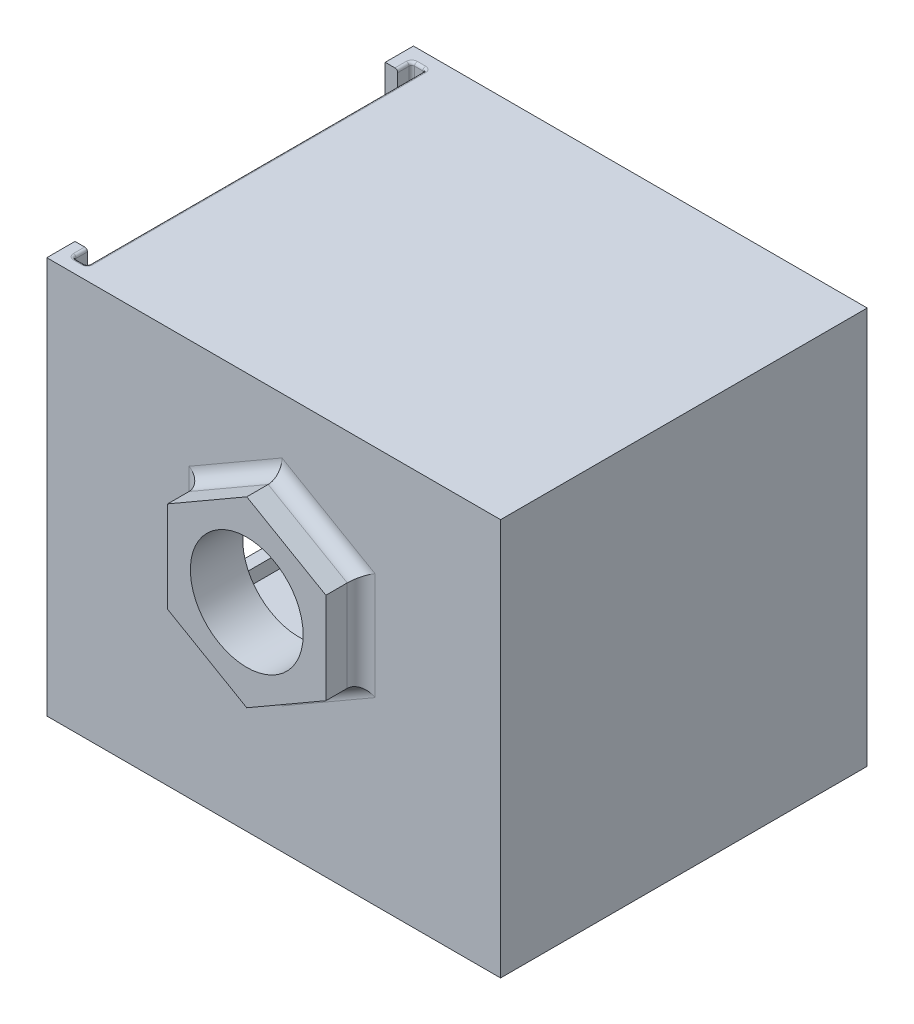
SolidWorks part; units mm, degrees
material "ABS"
ref_plane "Front Plane" through (0, 0, 0) normal (0, 0, 1) x (1, 0, 0)
ref_plane "Top Plane" through (0, 0, 0) normal (0, 1, 0) x (1, 0, 0)
ref_plane "Right Plane" through (0, 0, 0) normal (1, 0, 0) x (0, 0, -1)
sketch "Sketch1" plane through (0, 0, 0) normal (0, 1, 0) x (1, 0, 0)
  line L0 (-3.81, -5.08) -> (-3.81, 60.96)
  line L1 (0, 0) -> (71.12, 0)
  line L2 (0, 0) -> (0, 55.88)
  line L3 (0, 55.88) -> (71.12, 55.88)
  line L4 (71.12, 0) -> (71.12, 55.88)
  line L5 (-3.81, 60.96) -> (74.93, 60.96)
  line L6 (74.93, -5.08) -> (74.93, 60.96)
  line L7 (-3.81, -5.08) -> (74.93, -5.08)
  dimension "D1" = 55.88
  dimension "D2" = 71.12
  dimension "D4" = 5.08
  dimension "D5" = 5.08
  dimension "D6" = 3.81
  dimension "D3" = 3.81
extrude "Boss-Extrude1" add sketch "Sketch1" along normal blind 63.5
sketch "Sketch2" plane through (0, 0, 0) normal (0, 1, 0) x (1, 0, 0)
  line L0 (-3.81, 60.96) -> (-3.81, -5.08) construction
  line L1 (-3.81, 60.96) -> (-3.81, -5.08)
  line L2 (74.93, 60.96) -> (-3.81, 60.96) construction
  line L3 (-3.81, -5.08) -> (74.93, -5.08) construction
  line L4 (74.93, -5.08) -> (74.93, 60.96) construction
  line L5 (74.93, 60.96) -> (-3.81, 60.96)
  line L6 (-3.81, -5.08) -> (74.93, -5.08)
  line L7 (74.93, -5.08) -> (74.93, 60.96)
extrude "Boss-Extrude2" add sketch "Sketch2" against normal blind 4
sketch "Sketch3" plane through (-3.81, 0, 0) normal (-1, 0, 0) x (0, 0, 1)
  line L0 (-60.96, 63.5) -> (-60.96, -4) construction
  line L1 (-60.96, -4) -> (5.08, -4) construction
  line L3 (-47.46, 4.89) -> (-47.46, 18.86)
  line L5 (-47.46, 4.89) -> (-33.998, 4.89)
  line L6 (-33.998, 4.89) -> (-33.998, 18.86)
  line L7 (-33.998, 18.86) -> (-47.46, 18.86)
  dimension "D1" = 13.5
  dimension "D2" = 13.462
  dimension "D3" = 8.89
  dimension "D4" = 13.97
extrude "Cut-Extrude1" cut sketch "Sketch3" against normal up to next
sketch "Sketch4" plane through (-3.81, 0, 0) normal (-1, 0, 0) x (0, 0, 1)
  line L0 (5.08, -4) -> (-2.54, -4)
  line L1 (-60.96, -4) -> (5.08, -4) construction
  line L2 (-2.54, -4) -> (-2.54, 4.89)
  line L3 (-2.54, 4.89) -> (-13.462, 4.89)
  line L4 (-13.462, 4.89) -> (-13.462, 18.86)
  line L6 (-13.462, 18.86) -> (-2.54, 18.86)
  line L7 (-2.54, 18.86) -> (-2.54, 4.89)
  line M8 (5.08, 63.5) -> (-60.96, 63.5)
  dimension "D1" = 7.62
  dimension "D2" = 8.89
  dimension "D3" = 10.922
  dimension "D4" = 13.97
extrude "Cut-Extrude2" cut sketch "Sketch4" against normal up to next contours L7 L4 L3 M8 region at (-3.81, 11.875, -8.001)
sketch "Sketch5" plane through (0, -4, 0) normal (0, -1, 0) x (-1, 0, 0)
  circle A1 centre (-65.9574, 8.0585) radius 1.3693
  circle A2 centre (-13.7574, 2.8585) radius 1.6 construction
  circle A3 centre (-65.9574, 36.0085) radius 1.6 construction
  circle A4 centre (-15.1574, 51.1585) radius 1.3692
  circle A5 centre (-65.9574, 36.0085) radius 1.3693
  circle A6 centre (-13.7574, 2.8585) radius 1.3692
  circle A7 centre (-65.9574, 8.0585) radius 1.6 construction
  circle A8 centre (-15.1574, 51.1585) radius 1.6 construction
extrude "Boss-Extrude3" [suppressed] add sketch "Sketch5" against normal blind 17
fillet "Fillet1" [suppressed] radius 3
sketch "Sketch11" plane through (0, 0, 5.08) normal (0, 0, 1) x (1, 0, 0)
  line L2 (76.0425, 38.1) -> (-4.9225, 38.1) construction
  line L4 (35.56, 63.5) -> (35.56, -4) construction
  line L5 (-3.81, 63.5) -> (74.93, 63.5) construction
  line L6 (-3.81, -4) -> (74.93, -4) construction
  line L7 (49.81, 46.3272) -> (49.81, 29.8728)
  line L8 (49.81, 29.8728) -> (35.56, 21.6455)
  line L9 (49.81, 46.3272) -> (35.56, 54.5545)
  line L10 (21.31, 29.8728) -> (35.56, 21.6455)
  line L11 (21.31, 46.3272) -> (21.31, 29.8728)
  line L12 (21.31, 46.3272) -> (35.56, 54.5545)
  circle A0 centre (35.56, 38.1) radius 14.25 construction
  point P15 (35.56, 38.1)
  point P17 (49.81, 38.1)
  dimension "D1" = 28.5
  dimension "D2" = 25.4
sketch "Sketch16" plane through (-3.81, 0, 0) normal (-1, 0, 0) x (0, 0, 1)
  line L1 (-60.96, 63.5) -> (5.08, 63.5)
  line L2 (-60.96, 63.5) -> (-60.96, -4)
  line L3 (-60.96, -4) -> (5.08, -4)
  line L4 (5.08, 63.5) -> (5.08, -4)
  line L5 (-47.46, 18.86) -> (-33.998, 18.86)
  line L6 (-47.46, 18.86) -> (-47.46, 4.89)
  line L7 (-47.46, 4.89) -> (-33.998, 4.89)
  line L8 (-33.998, 18.86) -> (-33.998, 4.89)
  line L9 (-13.462, 18.86) -> (-2.54, 18.86)
  line L10 (-13.462, 18.86) -> (-13.462, 4.89)
  line L11 (-13.462, 4.89) -> (-2.54, 4.89)
  line L12 (-2.54, 18.86) -> (-2.54, 4.89)
extrude "Boss-Extrude8" add sketch "Sketch16" along normal blind 3
sketch "Sketch17" plane through (0, 63.5, 0) normal (0, 1, 0) x (1, 0, 0)
  line L1 (-6.81, 60.96) -> (74.93, 60.96)
  line L2 (-6.81, 60.96) -> (-6.81, -5.08)
  line L3 (-6.81, -5.08) -> (74.93, -5.08)
  line L4 (74.93, 60.96) -> (74.93, -5.08)
extrude "Boss-Extrude9" add sketch "Sketch17" along normal blind 4
sketch "Sketch18" plane through (0, 67.5, 0) normal (0, 1, 0) x (1, 0, 0)
  line L0 (-6.81, -5.08) -> (74.93, -5.08) construction
  line L1 (-4.56, 58.42) -> (-2.06, 58.42)
  line L2 (-4.56, 58.42) -> (-4.56, 55.88)
  line L3 (-4.56, -2.54) -> (-2.06, -2.54)
  line L4 (-2.06, 58.42) -> (-2.06, 55.88)
  line L5 (-6.81, 55.88) -> (-4.56, 55.88)
  line L6 (-6.81, 60.96) -> (-6.81, -5.08) construction
  line L7 (-6.81, 55.88) -> (-6.81, 0)
  line L8 (74.93, 60.96) -> (-6.81, 60.96) construction
  line L9 (-6.81, 0) -> (-4.56, 0)
  line L10 (-4.56, 0) -> (-4.56, -2.54)
  line L11 (-2.06, 0) -> (-2.06, -2.54)
  line L12 (-2.06, 55.88) -> (0.19, 55.88)
  line L14 (-2.06, 0) -> (0.19, 0)
  line L15 (0.19, 55.88) -> (0.19, 0)
  dimension "D1" = 7
  dimension "D2" = 2.5
  dimension "D3" = 2.54
  dimension "D4" = 2.54
  dimension "D5" = 2.54
  dimension "D6" = 2.54
extrude "Cut-Extrude10" cut sketch "Sketch18" against normal blind 64.77
sketch "Sketch19" plane through (0, 2.73, 0) normal (0, 1, 0) x (1, 0, 0)
  line L1 (-4.56, 58.42) -> (-2.06, 58.42)
  line L2 (-4.56, 58.42) -> (-4.56, -2.54)
  line L3 (-4.56, -2.54) -> (-2.06, -2.54)
  line L4 (-2.06, 58.42) -> (-2.06, -2.54)
extrude "Cut-Extrude11" cut sketch "Sketch19" against normal blind 3
sketch "Sketch20" plane through (0.19, 0, 0) normal (-1, 0, 0) x (0, 0, 1)
  line L0 (0, 63.5) -> (0, 67.5) construction
  line L1 (-55.88, 67.5) -> (0, 67.5)
  line L2 (-55.88, 67.5) -> (-55.88, 63.5)
  line L3 (-55.88, 63.5) -> (0, 63.5)
  line L4 (0, 67.5) -> (0, 63.5)
  line L5 (0, 63.5) -> (-55.88, 63.5) construction
extrude "Boss-Extrude10" add sketch "Sketch20" along normal blind 2.25
sketch "Sketch21" plane through (0, 0, 0) normal (0, 1, 0) x (1, 0, 0)
  line L1 (0, 55.88) -> (71.12, 55.88)
  line L2 (0, 55.88) -> (0, 0)
  line L3 (0, 0) -> (71.12, 0)
  line L4 (71.12, 55.88) -> (71.12, 0)
extrude "Boss-Extrude11" add sketch "Sketch21" along normal blind 2.73
fillet "Fillet2" radius 0.5 13 edges at (-4.56, 67.5, 1.27) (-2.06, 67.5, -27.94) (-4.56, 67.5, -57.15) (-4.56, 33.615, 2.54) (-2.06, 33.615, 2.54) (-3.31, 67.5, 2.54) (-2.06, -0.27, -27.94) (-3.31, -0.27, 2.54) (-4.56, -0.27, -27.94) (-2.06, 33.615, -58.42) (-3.31, -0.27, -58.42) (-4.56, 33.615, -58.42) (-3.31, 67.5, -58.42)
extrude "Boss-Extrude12" add sketch "Sketch11" along normal blind 6.35
sketch "Sketch22" plane through (0, 0, 11.43) normal (0, 0, 1) x (1, 0, 0)
  line L0 (35.56, 54.5545) -> (35.56, 21.6455) construction
  circle A0 centre (35.56, 38.1) radius 10.16
extrude "Cut-Extrude12" cut sketch "Sketch22" against normal blind 11.35
sketch "Sketch23" plane through (0, 0, 0) normal (0, 0, -1) x (-1, 0, 0)
  line L0 (-49.81, 46.3272) -> (-35.56, 54.5545) construction
  line L1 (-49.81, 46.3272) -> (-35.56, 54.5545) construction
  line L2 (-21.31, 46.3272) -> (-21.31, 29.8728)
  line L3 (-21.31, 29.8728) -> (-35.56, 21.6455)
  line L4 (-21.31, 46.3272) -> (-35.56, 54.5545)
  line L5 (-49.81, 29.8728) -> (-35.56, 21.6455)
  line L6 (-49.81, 46.3272) -> (-49.81, 29.8728)
  line L7 (-49.81, 46.3272) -> (-35.56, 54.5545)
  line L13 (-49.81, 29.8728) -> (-49.81, 46.3272) construction
  point P0 (-49.81, 29.8728)
  point P2 (-37.9483, 52.9507)
  point P3 (-35.56, 54.5545)
  point P9 (-21.31, 38.1)
  point P16 (-35.935, 31.0407)
  point P17 (-35.935, 31.0407)
  point P19 (-35.56, 21.6455)
  point P20 (-35.935, 54.338)
  point P21 (-22.1598, 42.4865)
  point P22 (-30.4889, 55.6245)
  point P23 (0, 0)
  point P26 (-35.5125, 54.5786)
  point P27 (-49.81, 46.3272)
  point P29 (-49.81, 29.8728)
  point P32 (-24.0747, 41.2252)
  point P33 (-21.31, 29.8728)
extrude "Cut-Extrude13" cut sketch "Sketch23" against normal blind 2
fillet "Fillet3" radius 2.5 6 edges at (42.685, 25.7591, 5.08) (49.81, 38.1, 5.08) (42.685, 50.4409, 5.08) (28.435, 50.4409, 5.08) (28.435, 25.7591, 5.08) (21.31, 38.1, 5.08)
